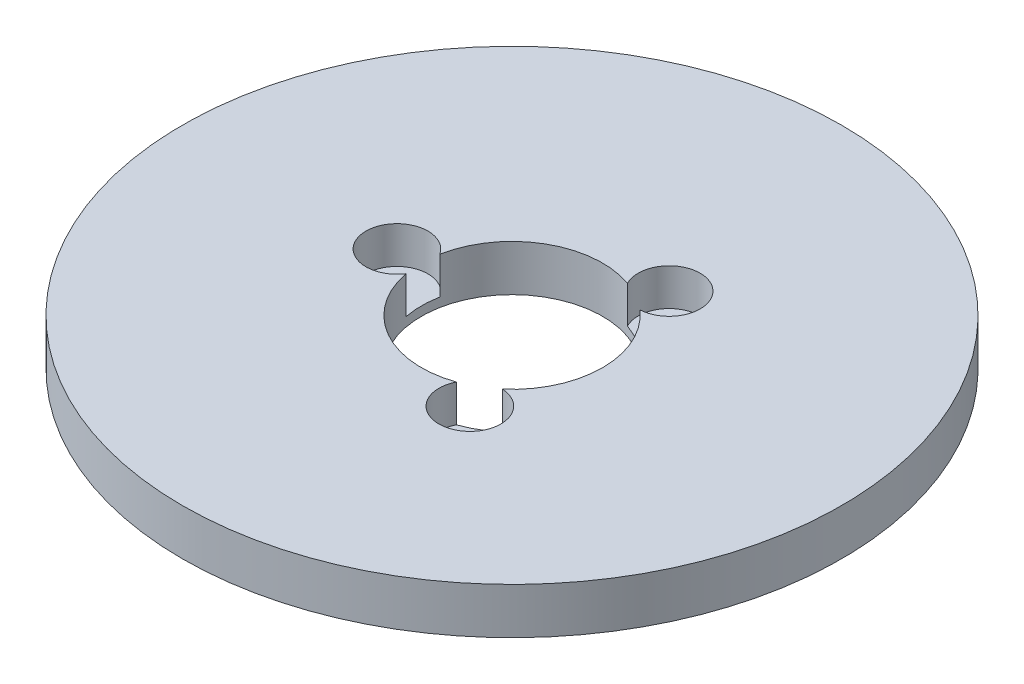
SolidWorks part; units mm, degrees
ref_plane "Front Plane" through (0, 0, 0) normal (0, 0, 1) x (1, 0, 0)
ref_plane "Top Plane" through (0, 0, 0) normal (0, 1, 0) x (1, 0, 0)
ref_plane "Right Plane" through (0, 0, 0) normal (1, 0, 0) x (0, 0, -1)
sketch "Sketch1" plane through (0, 0, 0) normal (0, 1, 0) x (1, 0, 0)
  circle A0 centre (0, 0) radius 100
  dimension "FLANGE_OD" = 200
extrude "Boss-Extrude1" add sketch "Sketch1" along normal blind 14
sketch "Sketch2" plane through (0, 0, 0) normal (0, 1, 0) x (1, 0, 0)
  circle A0 centre (0, 0) radius 27.5
  dimension "BORE_D" = 55
extrude "Cut-Extrude1" cut sketch "Sketch2" along normal through all
sketch "Sketch3" plane through (0, 14, 0) normal (0, 1, 0) x (1, 0, 0)
  circle A0 centre (0, 0) radius 34.9133 construction
  circle A1 centre (-34.9133, 0) radius 9.4046
  dimension "BOLT_D" = 18.8091
  dimension "BOLT_PCD" = 69.8266
extrude "Cut-Extrude2" cut sketch "Sketch3" against normal blind 11.248
pattern_circular "CirPattern1" count 3 over 360 about axis through (0, 0, 0) along (0, 1, 0) of "Cut-Extrude2"
